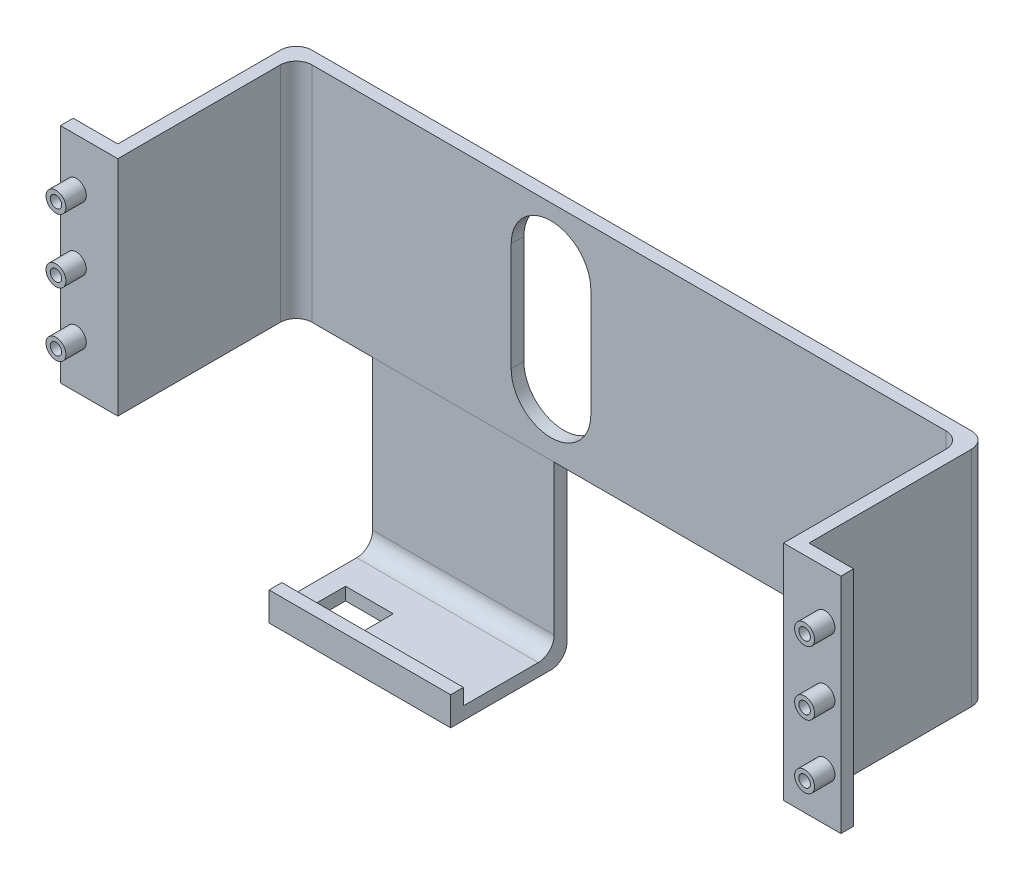
SolidWorks part; units mm, degrees
ref_plane "Front Plane" through (0, 0, 0) normal (0, 0, 1) x (1, 0, 0)
ref_plane "Top Plane" through (0, 0, 0) normal (0, 1, 0) x (1, 0, 0)
ref_plane "Right Plane" through (0, 0, 0) normal (1, 0, 0) x (0, 0, -1)
sketch "Sketch1" plane through (0, 0, 0) normal (0, 1, 0) x (1, 0, 0)
  line L0 (0, 0) -> (18, 0)
  line L1 (18, 0) -> (18, 56)
  line L2 (227, 56) -> (18, 56)
  line L3 (0, 0) -> (0, 4)
  line L4 (0, 4) -> (14, 4)
  line L5 (14, 4) -> (14, 60)
  line L6 (14, 60) -> (231, 60)
  line L7 (122.5, 41.705) -> (122.5, 38.705) construction
  line L8 (231, 4) -> (231, 60)
  line L9 (245, 4) -> (231, 4)
  line L10 (245, 0) -> (245, 4)
  line L11 (227, 0) -> (227, 56)
  line L12 (245, 0) -> (227, 0)
  point P12 (122.5, 60)
  point P16 (122.5, 56)
  dimension "D1" = 4
  dimension "D2" = 4
  dimension "D3" = 4
  dimension "D4" = 18
  dimension "D5" = 122.5
  dimension "D6" = 60
extrude "Boss-Extrude1" add sketch "Sketch1" along normal blind 70
sketch "Sketch2" plane through (0, 0, -4) normal (0, 0, -1) x (-1, 0, 0)
  line L0 (-245, 70) -> (-231, 70) construction
  line L1 (-122.5, 70) -> (-122.5, 0) construction
  line L2 (-231, 70) -> (-14, 70) construction
  line L3 (-231, 0) -> (-14, 0) construction
  circle A0 centre (-240.02, 55) radius 1.8
  circle A1 centre (-240.02, 35) radius 1.8
  circle A2 centre (-240.02, 15) radius 1.8
  circle A3 centre (-4.98, 15) radius 1.8
  circle A4 centre (-4.98, 35) radius 1.8
  circle A5 centre (-4.98, 55) radius 1.8
  dimension "D1" = 20
  dimension "D2" = 20
  dimension "D3" = 15
  dimension "D4" = 117.52
extrude "Cut-Extrude1" cut sketch "Sketch2" against normal through all
sketch "Sketch3" plane through (0, 0, -56) normal (0, 0, 1) x (1, 0, 0)
  line L0 (98, 52.6161) -> (98, 18.6333) construction
  line L1 (110.5, 52.6161) -> (110.5, 18.6333)
  line L2 (85.5, 52.6161) -> (85.5, 18.6333)
  line L3 (18, 70) -> (18, 0) construction
  arc A0 (110.5, 52.6161) -> (85.5, 52.6161) centre (98, 52.6161) ccw
  arc A1 (85.5, 18.6333) -> (110.5, 18.6333) centre (98, 18.6333) ccw
  point P2 (98, 35.6247)
  dimension "D1" = 80
extrude "Cut-Extrude2" cut sketch "Sketch3" against normal up to next
sketch "Sketch4" plane through (0, 0, -60) normal (0, 0, -1) x (-1, 0, 0)
  line L0 (-231, 0) -> (-14, 0) construction
  line L1 (-99, 0) -> (-42, 0)
  line L2 (-99, 0) -> (-99, -56)
  line L3 (-99, -56) -> (-42, -56)
  line L4 (-42, 0) -> (-42, -56)
  line L5 (-14, 70) -> (-14, 0) construction
  dimension "D1" = 56
  dimension "D2" = 57
  dimension "D3" = 28
extrude "Boss-Extrude2" add sketch "Sketch4" against normal blind 36.5 separate body
sketch "Sketch5" plane through (99, 0, 0) normal (1, 0, 0) x (0, 0, -1)
  line L0 (4, 0) -> (60, 0) construction
  line L1 (23.5, 0) -> (56, 0)
  line L2 (23.5, 0) -> (23.5, -47)
  line L3 (27.5, -52) -> (56, -52)
  line L4 (56, 0) -> (56, -52)
  line L5 (23.5, 0) -> (23.5, -56) construction
  line L6 (60, 0) -> (60, -56) construction
  line L7 (23.5, -56) -> (60, -56) construction
  line L11 (23.5, -47) -> (27.5, -47)
  line L12 (27.5, -52) -> (27.5, -47)
  dimension "D1" = 4
  dimension "D2" = 4
  dimension "D3" = 4
  dimension "D4" = 5
extrude "Cut-Extrude3" cut sketch "Sketch5" against normal through all
fillet "Fillet1" radius 5 4 edges at (227, 35, -56) (18, 35, -56) (14, 35, -60) (231, 35, -60)
fillet "Fillet2" radius 5 2 edges at (70.5, -56, -60) (70.5, -52, -56)
sketch "Sketch6" plane through (0, -56, 0) normal (0, -1, 0) x (1, 0, 0)
  line L0 (42, -23.5) -> (42, -55) construction
  line L1 (48, -31.5) -> (63, -31.5)
  line L2 (48, -31.5) -> (48, -41.5)
  line L3 (48, -41.5) -> (63, -41.5)
  line L4 (63, -31.5) -> (63, -41.5)
  line L5 (99, -23.5) -> (42, -23.5) construction
  dimension "D1" = 15
  dimension "D2" = 10
  dimension "D3" = 6
  dimension "D4" = 8
extrude "Cut-Extrude4" cut sketch "Sketch6" against normal through all
sketch "Sketch7" plane through (0, 0, 0) normal (0, 0, 1) x (1, 0, 0)
  line L0 (122.5, 70) -> (122.5, 0) construction
  line L1 (23, 70) -> (222, 70) construction
  line L2 (23, 0) -> (222, 0) construction
  circle A0 centre (4.98, 55) radius 3.125
  circle A1 centre (4.98, 35) radius 3.125
  circle A2 centre (4.98, 15) radius 3.125
  circle A3 centre (4.98, 55) radius 1.8
  circle A4 centre (4.98, 35) radius 1.8
  circle A5 centre (4.98, 15) radius 1.8
  circle A6 centre (240.02, 15) radius 1.8
  circle A7 centre (240.02, 35) radius 1.8
  circle A8 centre (240.02, 55) radius 1.8
  circle A9 centre (240.02, 15) radius 3.125
  circle A10 centre (240.02, 35) radius 3.125
  circle A11 centre (240.02, 55) radius 3.125
extrude "Boss-Extrude4" add sketch "Sketch7" along normal blind 6.4
